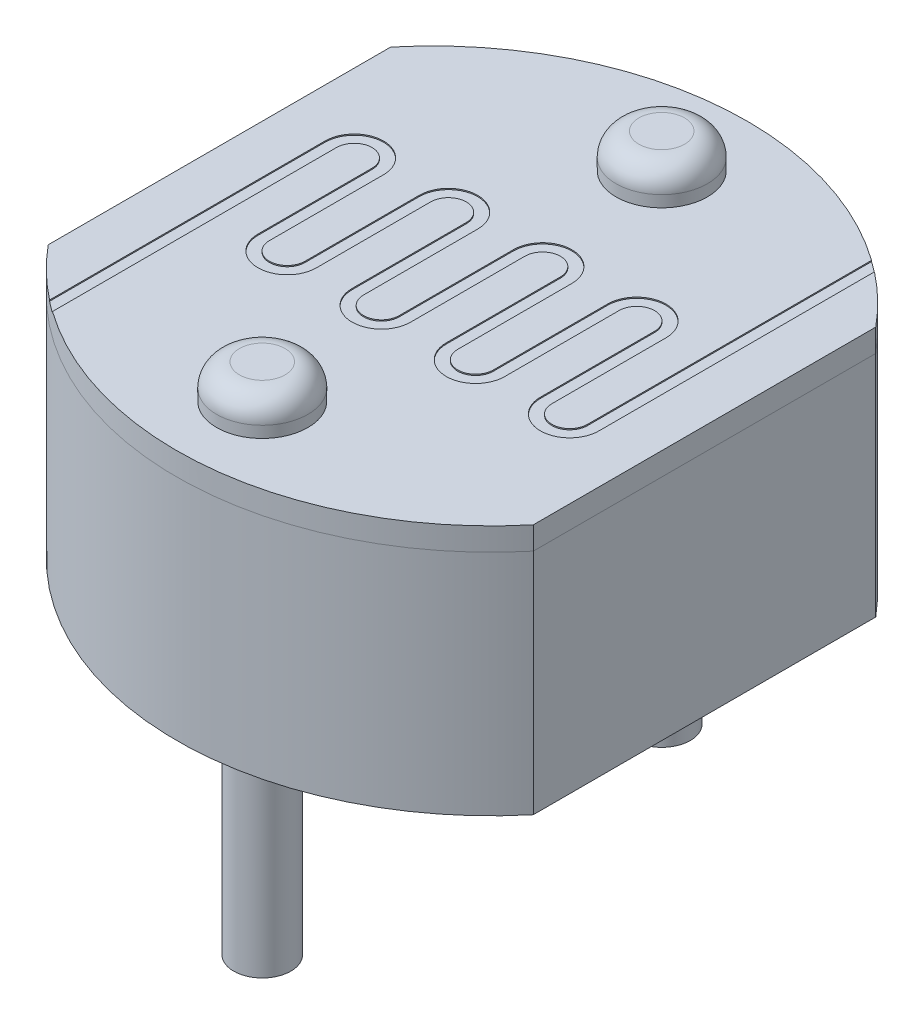
SolidWorks part; units mm, degrees
material "6061-T6 (SS)"
ref_plane "Front Plane" through (0, 0, 0) normal (0, 0, 1) x (1, 0, 0)
ref_plane "Top Plane" through (0, 0, 0) normal (0, 1, 0) x (1, 0, 0)
ref_plane "Right Plane" through (0, 0, 0) normal (1, 0, 0) x (0, 0, -1)
sketch "Sketch1" plane through (0, 0, 0) normal (0, 1, 0) x (1, 0, 0)
  line L0 (0, 1.5) -> (0, -1.5) construction
  line L1 (-2.125, 1.5) -> (2.125, 1.5) construction
  line L2 (-2.125, 1.5) -> (-2.125, -1.5)
  line L3 (-2.125, -1.5) -> (2.125, -1.5) construction
  line L4 (2.125, 1.5) -> (2.125, -1.5)
  line L5 (0, 1.5) -> (0, 2.5) construction
  line L6 (0, -1.5) -> (0, -2.5) construction
  arc A0 (-2.125, 1.5) -> (2.125, 1.5) centre (0, -0.2578) cw
  arc A1 (-2.125, -1.5) -> (2.125, -1.5) centre (0, 0.2578) ccw
  dimension "D1" = 5
  dimension "D2" = 4.25
  dimension "D3" = 3
extrude "Boss-Extrude1" add sketch "Sketch1" along normal blind 2
sketch "Sketch2" plane through (0, 2, 0) normal (0, 1, 0) x (1, 0, 0)
  line L2 (-2.125, 1.5) -> (-2.125, -1.5)
  line L3 (2.125, -1.5) -> (2.125, 1.5)
  line L4 (-2.125, 1.5) -> (-2.125, -1.5)
  line L5 (2.125, -1.5) -> (2.125, 1.5)
  arc A2 (2.125, 1.5) -> (-2.125, 1.5) centre (0, -0.2578) ccw
  arc A3 (-2.125, -1.5) -> (2.125, -1.5) centre (0, 0.2578) ccw
  arc A4 (2.125, 1.5) -> (-2.125, 1.5) centre (0, -0.2578) ccw
  arc A5 (-2.125, -1.5) -> (2.125, -1.5) centre (0, 0.2578) ccw
  dimension "D1" = 0
extrude "Boss-Extrude2" add sketch "Sketch2" along normal blind 0.2 separate body
sketch "Sketch3" plane through (0, 0, 0) normal (0, -1, 0) x (1, 0, 0)
  line L0 (0, 1.75) -> (0, -1.75) construction
  circle A0 centre (0, 1.75) radius 0.4
  circle A1 centre (0, -1.75) radius 0.4
  dimension "D2" = 0.8
  dimension "D1" = 3.5
extrude "Boss-Extrude4" add sketch "Sketch3" against normal blind 2.5
sketch "Sketch4" plane through (0, 0, 0) normal (0, -1, 0) x (1, 0, 0)
  circle A0 centre (0, 1.75) radius 0.25
  circle A1 centre (0, -1.75) radius 0.25
  dimension "D1" = 0.5
extrude "Boss-Extrude5" add sketch "Sketch4" along normal blind 2
fillet "Fillet1" radius 0.5 2 edges at (0, 0, -2) (0, 0, 1.5)
fillet "Fillet2" radius 0.2 2 edges at (0, 2.5, -2.15) (0, 2.5, 1.35)
sketch "Sketch5" plane through (0, 2.2, 0) normal (0, 1, 0) x (1, 0, 0)
  line L0 (0, 0.5) -> (0, -0.5)
  line L1 (0, 0) -> (0.4125, 0) construction
  line L2 (0.4125, 0) -> (0.825, 0) construction
  line L3 (0, 0) -> (-0.4125, 0) construction
  line L4 (-0.4125, 0) -> (-0.825, 0) construction
  line L5 (-0.825, 0) -> (-1.2375, 0) construction
  line L6 (-1.2375, 0) -> (-1.65, 0) construction
  line L7 (0.825, 0) -> (1.2375, 0) construction
  line L8 (1.2375, 0) -> (1.65, 0) construction
  line L9 (0.4125, 0.5) -> (0.4125, -0.5)
  line L10 (-0.4125, 0.5) -> (-0.4125, -0.5)
  line L11 (-0.825, 0.5) -> (-0.825, -0.5)
  line L12 (-1.2375, 0.5) -> (-1.2375, -0.5)
  line L13 (0.825, 0.5) -> (0.825, -0.5)
  line L14 (1.2375, 0.5) -> (1.2375, -0.5)
  line L15 (-1.2375, -0.5) -> (-0.825, -0.5) construction
  line L16 (-0.825, -0.5) -> (-0.4125, -0.5) construction
  line L17 (-0.4125, -0.5) -> (0, -0.5) construction
  line L18 (0, -0.5) -> (0.4125, -0.5) construction
  line L19 (0.4125, -0.5) -> (0.825, -0.5) construction
  line L20 (0.825, -0.5) -> (1.2375, -0.5) construction
  line L21 (1.65, 1.9519) -> (1.65, -0.5)
  line L22 (1.2375, -0.5) -> (1.65, -0.5) construction
  line L23 (-1.65, 0.5) -> (-1.65, -1.9519)
  line L24 (-1.65, 0.5) -> (-1.2375, 0.5) construction
  line L25 (-1.2375, 0.5) -> (-0.825, 0.5) construction
  line L26 (-0.825, 0.5) -> (-0.4125, 0.5) construction
  line L27 (-0.4125, 0.5) -> (0, 0.5) construction
  line L28 (0, 0.5) -> (0.4125, 0.5) construction
  line L29 (0.4125, 0.5) -> (0.825, 0.5) construction
  line L30 (0.825, 0.5) -> (1.2375, 0.5) construction
  line L31 (1.65, 1.9519) -> (1.65, 2.5)
  line L32 (-1.65, -1.9519) -> (-1.65, -2.5)
  line L33 (0, -1.75) -> (0, -2.5) construction
  line L34 (0, -2.5) -> (-1.65, -2.5) construction
  line L35 (0, 1.75) -> (0, 2.5) construction
  line L36 (0, 2.5) -> (1.65, 2.5) construction
  arc A1 (-2.125, -1.5) -> (2.125, -1.5) centre (0, 0.2578) ccw construction
  arc A2 (2.125, 1.5) -> (-2.125, 1.5) centre (0, -0.2578) ccw construction
  arc A3 (-1.2375, 0.5) -> (-1.65, 0.5) centre (-1.4437, 0.5) ccw
  arc A4 (-1.2375, -0.5) -> (-0.825, -0.5) centre (-1.0312, -0.5) ccw
  arc A5 (-0.4125, 0.5) -> (-0.825, 0.5) centre (-0.6188, 0.5) ccw
  arc A6 (-0.4125, -0.5) -> (0, -0.5) centre (-0.2063, -0.5) ccw
  arc A7 (0.4125, 0.5) -> (0, 0.5) centre (0.2062, 0.5) ccw
  arc A8 (0.4125, -0.5) -> (0.825, -0.5) centre (0.6187, -0.5) ccw
  arc A10 (1.2375, 0.5) -> (0.825, 0.5) centre (1.0312, 0.5) ccw
  arc A11 (1.2375, -0.5) -> (1.65, -0.5) centre (1.4437, -0.5) ccw
  point P43 (0, 0)
  dimension "D1" = 3.3
  dimension "D2" = 1
extrude "Cut-Extrude-Thin1" cut sketch "Sketch5" against normal blind 0.01 thin thin type mid plane wall 0.1
